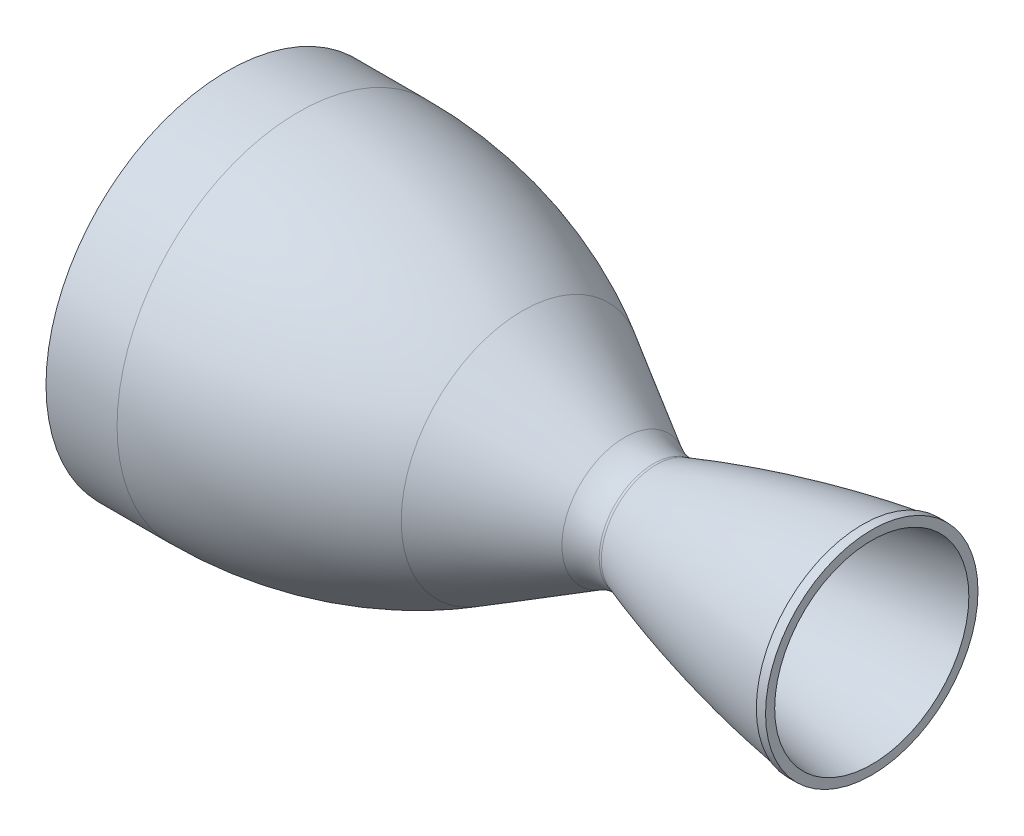
SolidWorks part; units mm, degrees
ref_plane "Front Plane" through (0, 0, 0) normal (0, 0, 1) x (1, 0, 0)
ref_plane "Top Plane" through (0, 0, 0) normal (0, 1, 0) x (1, 0, 0)
ref_plane "Right Plane" through (0, 0, 0) normal (1, 0, 0) x (0, 0, -1)
sketch "Model" plane through (0, 0, 0) normal (0, 0, 1) x (1, 0, 0)
  line L0 (0, 94.6788) -> (39.1107, 94.6788)
  line L1 (0, 99.7588) -> (39.1107, 99.7588)
  line L2 (159.903, 62.3126) -> (215.9628, 29.9464)
  line L3 (162.443, 66.712) -> (218.5028, 34.3458)
  line L4 (0, 0) -> (354.6796, 0) construction
  line L5 (0, 99.7588) -> (0, 94.6788)
  line L7 (354.6796, 53.43) -> (354.6796, 58.4606)
  line L10 (349.5996, 58.4606) -> (349.5996, 57.8307)
  line L11 (349.5996, 58.4606) -> (354.6796, 58.4606)
  arc A0 (159.903, 62.3126) -> (39.1107, 94.6788) centre (39.1107, -146.9057) ccw
  arc A1 (162.443, 66.712) -> (39.1107, 99.7588) centre (39.1107, -146.9057) ccw
  arc A2 (215.9628, 29.9464) -> (234.6643, 24.9354) centre (234.6643, 62.3384) ccw
  arc A3 (218.5028, 34.3458) -> (234.6643, 30.0154) centre (234.6643, 62.3384) ccw
  arc A4 (234.6643, 24.9354) -> (237.7572, 25.4515) centre (234.6643, 34.4607) ccw
  arc A5 (234.6643, 30.0154) -> (236.1077, 30.2562) centre (234.6643, 34.4607) ccw
  spline S0 degree 2 poles (237.7572, 25.4515) (294.7005, 45.0005) (354.6796, 53.43) knots 0 0 0 1 1 1
  spline S1 degree 1 poles (236.1077, 30.2562) (353.9726, 58.4606) knots 0 0 1 1 construction
  spline S2 degree 2 poles (236.1077, 30.2562) (254.376, 36.5278) (310.1142, 51.9378) (349.5994, 57.8317) (352.3312, 58.2299) (353.9726, 58.4606) knots 0 0 0 0.31825 0.954749 0.972849 1 1 1 only from (236.1077, 30.2562) to (349.5996, 57.8307)
  dimension "D2" = 99.7588
  dimension "D3" = 354.6796
  dimension "D4" = 5.08
  dimension "D5" = 5.0306
  dimension "D6" = 58.4606
  dimension "D1" = 5.08
revolve "Revolve1" add sketch "Model" angle 360 about L4
